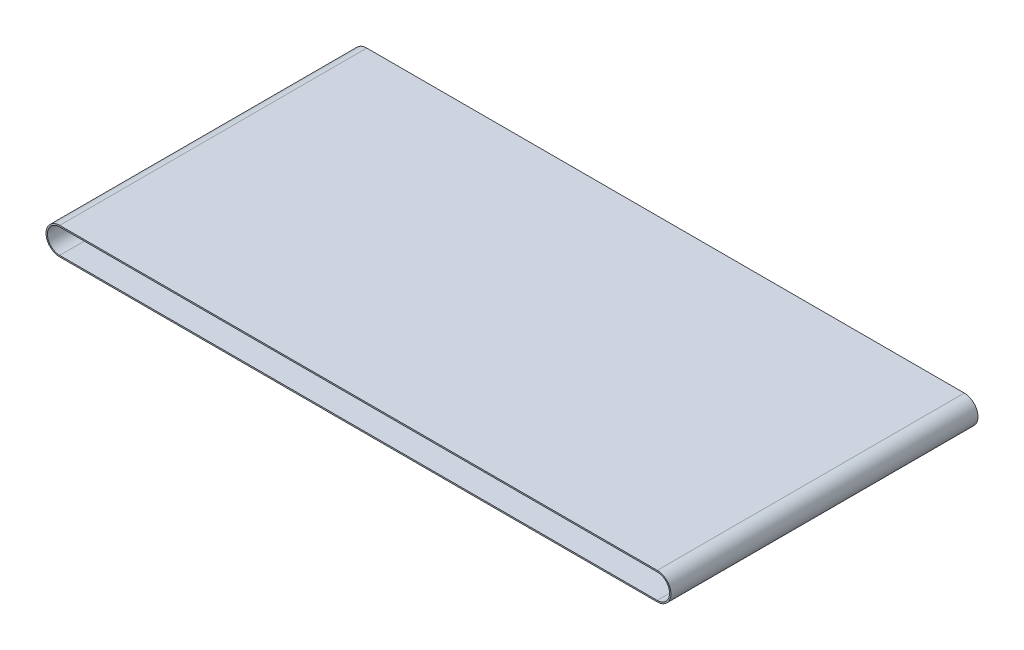
SolidWorks part; units mm, degrees
ref_plane "Plan de face" through (0, 0, 0) normal (0, 0, 1) x (1, 0, 0)
ref_plane "Plan de dessus" through (0, 0, 0) normal (0, 1, 0) x (1, 0, 0)
ref_plane "Plan de droite" through (0, 0, 0) normal (1, 0, 0) x (0, 0, -1)
sketch "Esquisse1" plane through (0, 0, 0) normal (0, 0, 1) x (1, 0, 0)
  line L1 (-554.6, 25.4) -> (554.6, 25.4)
  line L3 (-554.6, -25.4) -> (554.6, -25.4)
  arc A0 (-554.6, -25.4) -> (-554.6, 25.4) centre (-554.6, 0) cw
  arc A1 (554.6, 25.4) -> (554.6, -25.4) centre (554.6, 0) cw
  point P6 (-580, 0)
  point P7 (580, 0)
  point P9 (0, 25.4)
  dimension "D1" = 50.8
  dimension "D2" = 1160
extrude "Boss.-Extru.1" add sketch "Esquisse1" along normal mid plane 570
sketch "Esquisse2" plane through (0, 0, 285) normal (0, 0, 1) x (1, 0, 0)
  line L0 (554.6, 25.4) -> (-554.6, 25.4) construction
  line L1 (-554.6, 22.86) -> (554.6, 22.86)
  line L3 (-554.6, -22.86) -> (554.6, -22.86)
  line L5 (-554.6, -25.4) -> (554.6, -25.4) construction
  arc A0 (-554.6, 22.86) -> (-554.6, -22.86) centre (-554.6, 0) ccw
  arc A1 (554.6, 22.86) -> (554.6, -22.86) centre (554.6, 0) cw
  dimension "D1" = 2.54
  dimension "D2" = 2.54
  dimension "D3" = 45.72
extrude "Enlèv. mat.-Extru.1" cut sketch "Esquisse2" against normal up to next
